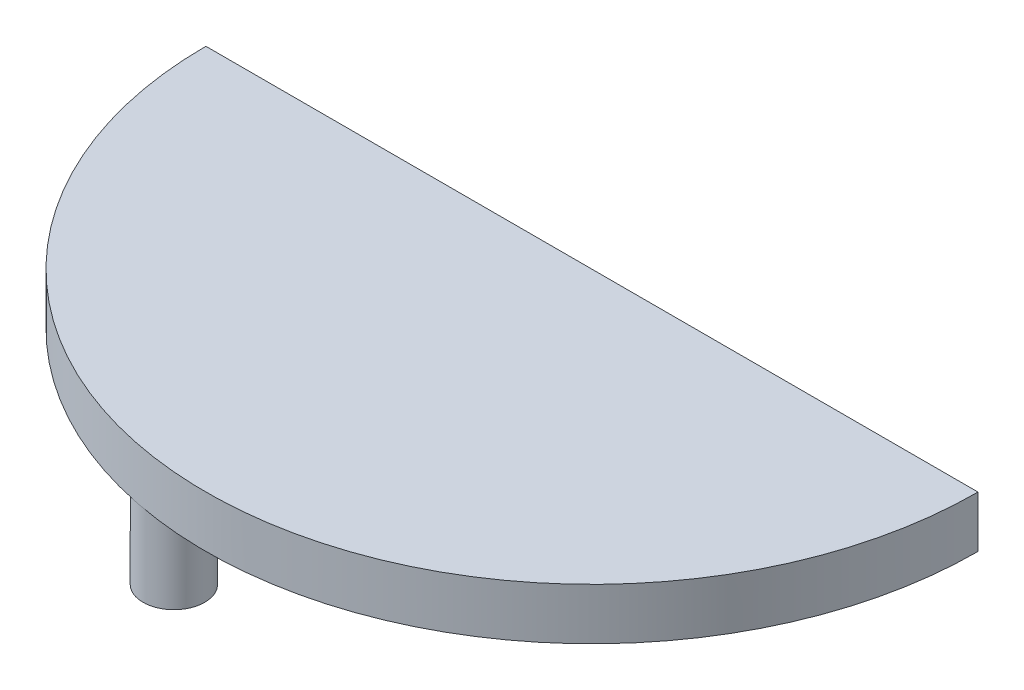
SolidWorks part; units mm, degrees
ref_plane "Ebene vorne" through (0, 0, 0) normal (0, 0, 1) x (1, 0, 0)
ref_plane "Ebene oben" through (0, 0, 0) normal (0, 1, 0) x (1, 0, 0)
ref_plane "Ebene rechts" through (0, 0, 0) normal (1, 0, 0) x (0, 0, -1)
sketch "Skizze1" plane through (0, 0, 0) normal (0, 1, 0) x (1, 0, 0)
  line L0 (0, 0) -> (-75, 0)
  arc A0 (-75, 0) -> (0, 0) centre (-37.5, 0) ccw
extrude "Aufsatz-Linear austragen1" add sketch "Skizze1" along normal blind 5
sketch "Skizze2" plane through (0, 0, 0) normal (0, -1, 0) x (1, 0, 0)
  line L0 (-37.5, 0) -> (-37.5, 37.5) construction
  line L1 (0, 0) -> (-75, 0) construction
  arc A0 (0, 0) -> (-75, 0) centre (-37.5, 0) ccw construction
  circle A1 centre (-44.2754, 33.8309) radius 3
  point P9 (-40.5709, 34.3088)
  point P10 (-41.4866, 34.1265)
  point P11 (-43.1915, 33.3678)
  point P12 (-44.3812, 33.1737)
  point P13 (-44.2754, 33.8309)
extrude "Aufsatz-Linear austragen2" add sketch "Skizze2" along normal blind 8
ref_plane "Ebene1" through (-44.2754, 0, 0) normal (1, 0, 0) x (0, 1, 0)
